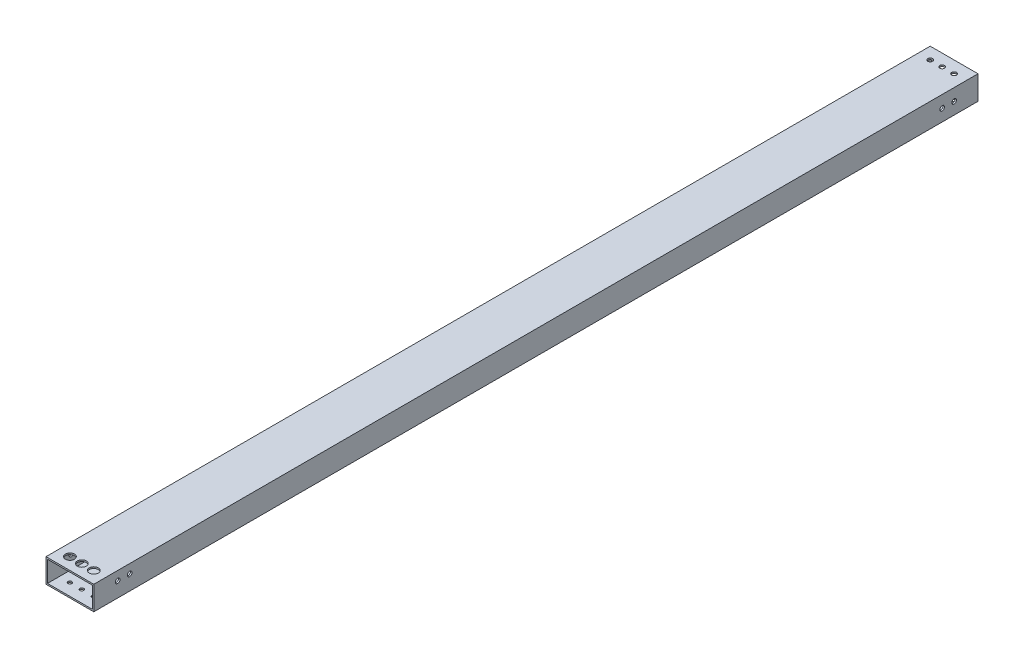
SolidWorks part; units mm, degrees
material "6061-T6 (SS)"
ref_plane "Front Plane" through (0, 0, 0) normal (0, 0, 1) x (1, 0, 0)
ref_plane "Top Plane" through (0, 0, 0) normal (0, 1, 0) x (1, 0, 0)
ref_plane "Right Plane" through (0, 0, 0) normal (1, 0, 0) x (0, 0, -1)
sketch "Sketch1" plane through (0, 0, 0) normal (0, 0, 1) x (1, 0, 0)
  line L0 (-23.8125, 11.1125) -> (23.8125, 11.1125)
  line L1 (-25.4, -12.7) -> (25.4, -12.7)
  line L2 (-25.4, -12.7) -> (-25.4, 12.7)
  line L3 (-25.4, 12.7) -> (25.4, 12.7)
  line L4 (25.4, -12.7) -> (25.4, 12.7)
  line L5 (-25.4, -12.7) -> (25.4, 12.7) construction
  line L6 (-25.4, 12.7) -> (25.4, -12.7) construction
  line L7 (23.8125, -11.1125) -> (23.8125, 11.1125)
  line L8 (-23.8125, -11.1125) -> (23.8125, -11.1125)
  line L9 (-23.8125, -11.1125) -> (-23.8125, 11.1125)
  point P0 (0, 0)
  dimension "D1" = 50.8
  dimension "D2" = 25.4
  dimension "D3" = 1.5875
extrude "Boss-Extrude1" add sketch "Sketch1" along normal mid plane 939.8
sketch "Sketch4" plane through (0, 12.7, 0) normal (0, 1, 0) x (1, 0, 0)
  line L0 (25.4, -469.9) -> (-25.4, -469.9) construction
  circle A0 centre (-12.7, -457.2) radius 4.826
  circle A1 centre (0, -457.2) radius 4.826
  circle A2 centre (12.7, -457.2) radius 4.826
  dimension "D1" = 9.652
  dimension "D2" = 12.7
  dimension "D3" = 12.7
  dimension "D4" = 12.7
extrude "Cut-Extrude3" cut sketch "Sketch4" against normal up to surface (1.5875 mm away) contours A0 | A1 | A2 region at (-12.7, 12.7, 457.2) region at (0, 12.7, 457.2) region at (12.7, 12.7, 457.2) up to face at (0, 11.1125, 0)
sketch "Sketch5" plane through (0, -12.7, 0) normal (0, -1, 0) x (1, 0, 0)
  circle A0 centre (-12.7, 457.2) radius 4.826 construction
  circle A1 centre (0, 457.2) radius 4.826 construction
  circle A2 centre (12.7, 457.2) radius 4.826 construction
  circle A3 centre (-12.7, 457.2) radius 4.826
  circle A4 centre (0, 457.2) radius 4.826
  circle A5 centre (12.7, 457.2) radius 4.826
  circle A6 centre (-12.7, 457.2) radius 2.0193
  circle A7 centre (0, 457.2) radius 2.0193
  circle A8 centre (12.7, 457.2) radius 2.0193
  dimension "D1" = 4.0386
  dimension "D2" = 4.0386
  dimension "D3" = 4.0386
extrude "Cut-Extrude4" cut sketch "Sketch5" against normal up to surface (1.5875 mm away) contours A8 | A7 | A6 region at (-12.7, -12.7, 457.2) region at (0, -12.7, 457.2) region at (12.7, -12.7, 457.2) up to face at (0, -11.1125, 0)
sketch "Sketch6" plane through (0, -12.7, 0) normal (0, -1, 0) x (1, 0, 0)
  line L0 (-25.4, -469.9) -> (25.4, -469.9) construction
  circle A0 centre (-12.7, -457.2) radius 2.5527
  circle A1 centre (0, -457.2) radius 2.5527
  circle A2 centre (12.7, -457.2) radius 2.5527
  dimension "D1" = 5.1054
  dimension "D2" = 12.7
  dimension "D3" = 12.7
  dimension "D4" = 12.7
extrude "Cut-Extrude5" cut sketch "Sketch6" against normal through all contours A2 | A1 | A0 region at (-12.7, -12.7, -457.2) region at (0, -12.7, -457.2) region at (12.7, -12.7, -457.2)
sketch "Sketch7" plane through (25.4, 0, 0) normal (1, 0, 0) x (0, 0, -1)
  line L0 (-469.9, -12.7) -> (-469.9, 12.7) construction
  line L2 (469.9, -12.7) -> (469.9, 12.7) construction
  line L3 (-469.9, -12.7) -> (469.9, -12.7) construction
  circle A0 centre (-457.2, 3.175) radius 2.4892
  circle A1 centre (-444.5, 3.175) radius 2.4892
  circle A2 centre (-431.8, 3.175) radius 2.4892
  circle A3 centre (-419.1, 3.175) radius 2.4892
  circle A4 centre (457.2, 0) radius 2.4892
  circle A5 centre (444.5, 0) radius 2.4892
  circle A6 centre (431.8, 0) radius 2.4892
  dimension "D1" = 4.9784
  dimension "D7" = 4.9784
  dimension "D8" = 12.7
  dimension "D2" = 12.7
  dimension "D3" = 12.7
  dimension "D4" = 12.7
  dimension "D5" = 12.7
  dimension "D6" = 15.875
  dimension "D9" = 12.7
  dimension "D10" = 12.7
  dimension "D11" = 12.7
extrude "Cut-Extrude6" cut sketch "Sketch7" against normal through all contours A6 | A5 | A1 | A2 region at (25.4, 3.175, 444.5) region at (25.4, 3.175, 431.8) region at (25.4, 0, -444.5) region at (25.4, 0, -431.8)
sketch "Sketch9" plane through (0, 12.7, 0) normal (0, 1, 0) x (1, 0, 0)
  line L0 (25.4, -469.9) -> (-25.4, -469.9) construction
  circle A0 centre (-12.7, -419.1) radius 2.5527
  circle A1 centre (0, -419.1) radius 2.5527
  circle A2 centre (12.7, -419.1) radius 2.5527
  dimension "D1" = 5.1054
  dimension "D2" = 12.7
  dimension "D3" = 12.7
  dimension "D4" = 50.8
extrude "Cut-Extrude7" [suppressed] cut sketch "Sketch9" against normal through all
